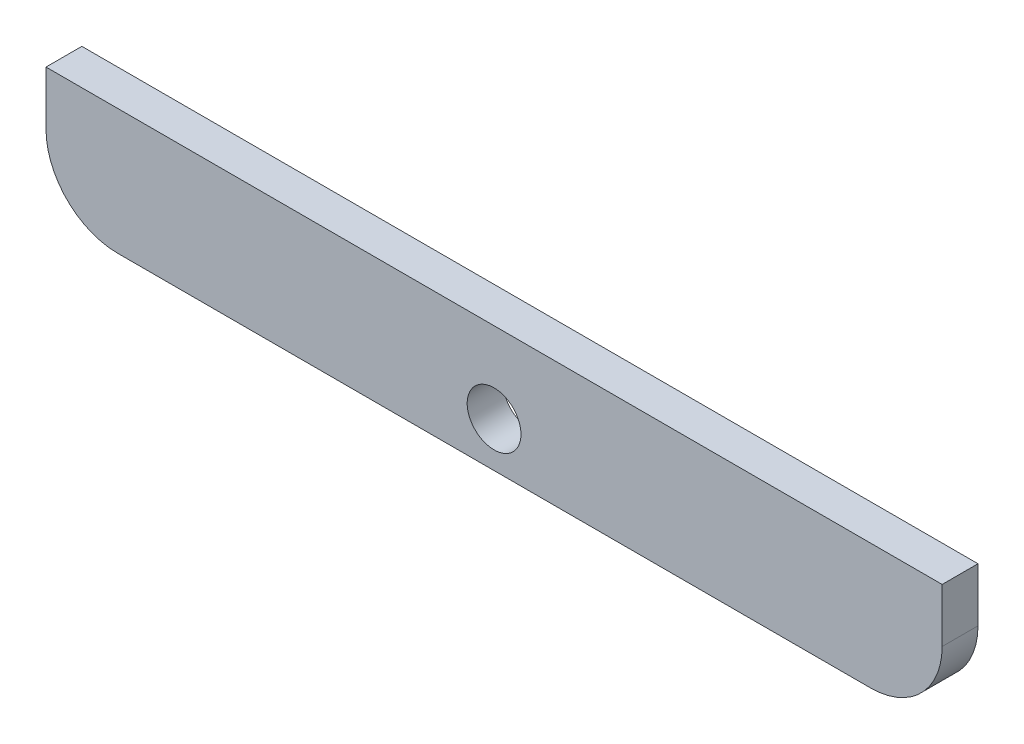
SolidWorks part; units mm, degrees
ref_plane "Front Plane" through (0, 0, 0) normal (0, 0, 1) x (1, 0, 0)
ref_plane "Top Plane" through (0, 0, 0) normal (0, 1, 0) x (1, 0, 0)
ref_plane "Right Plane" through (0, 0, 0) normal (1, 0, 0) x (0, 0, -1)
sketch "Sketch1" plane through (0, 0, 0) normal (0, 0, 1) x (1, 0, 0)
  line L1 (-21, -2.5) -> (21, -2.5)
  line L10 (-25, 1.5) -> (-25, 4.5)
  line L11 (-25, 4.5) -> (25, 4.5)
  line L12 (25, 1.5) -> (25, 4.5)
  circle A0 centre (0, 0) radius 1.5
  arc A1 (25, 1.5) -> (21, -2.5) centre (21, 1.5) cw
  arc A2 (-21, -2.5) -> (-25, 1.5) centre (-21, 1.5) cw
  point P0 (0, 0)
  point P1 (0, 0)
  point P2 (0, 0)
  point P3 (0, 0)
  dimension "D1" = 3
  dimension "D4" = 4
  dimension "D2" = 2.5
  dimension "D3" = 7
  dimension "D5" = 50
  dimension "D6" = 25
extrude "Boss-Extrude1" add sketch "Sketch1" along normal mid plane 2
